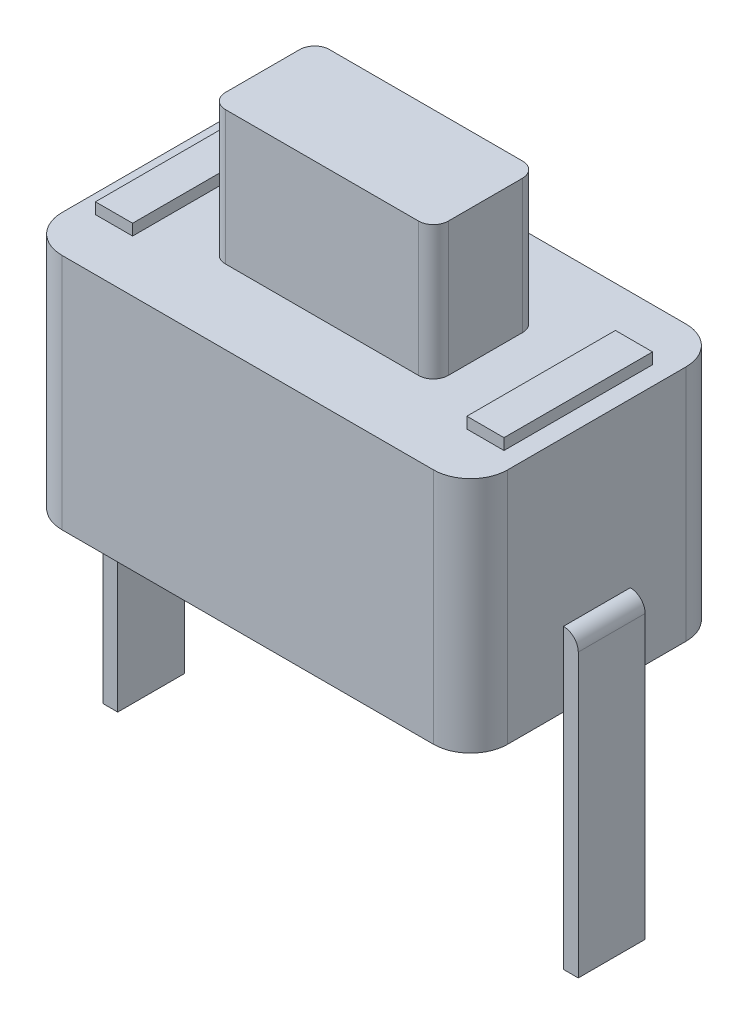
SolidWorks part; units mm, degrees
ref_plane "Front Plane" through (0, 0, 0) normal (0, 0, 1) x (1, 0, 0)
ref_plane "Top Plane" through (0, 0, 0) normal (0, 1, 0) x (1, 0, 0)
ref_plane "Right Plane" through (0, 0, 0) normal (1, 0, 0) x (0, 0, -1)
sketch "Sketch1" plane through (0, 0, 0) normal (0, 1, 0) x (1, 0, 0)
  line L1 (3, -1.7) -> (-3, -1.7)
  line L2 (3, -1.7) -> (3, 1.7)
  line L3 (3, 1.7) -> (-3, 1.7)
  line L4 (-3, -1.7) -> (-3, 1.7)
  line L5 (3, -1.7) -> (-3, 1.7) construction
  line L6 (3, 1.7) -> (-3, -1.7) construction
  point P0 (0, 0)
  dimension "D1" = 6
  dimension "D2" = 3.4
extrude "Boss-Extrude1" add sketch "Sketch1" along normal blind 3.2
sketch "Sketch2" plane through (0, 3.2, 0) normal (0, 1, 0) x (1, 0, 0)
  line L0 (-3, 1.7) -> (-3, -1.7) construction
  line L1 (1.5, -0.7) -> (-1.5, -0.7)
  line L2 (1.5, -0.7) -> (1.5, 0.7)
  line L3 (1.5, 0.7) -> (-1.5, 0.7)
  line L4 (-1.5, -0.7) -> (-1.5, 0.7)
  line L5 (1.5, -0.7) -> (-1.5, 0.7) construction
  line L6 (1.5, 0.7) -> (-1.5, -0.7) construction
  line L7 (-2.25, -1) -> (-2.75, -1)
  line L8 (-2.25, -1) -> (-2.25, 1)
  line L9 (-2.25, 1) -> (-2.75, 1)
  line L10 (-2.75, -1) -> (-2.75, 1)
  line L11 (-2.25, -1) -> (-2.75, 1) construction
  line L12 (-2.25, 1) -> (-2.75, -1) construction
  line L13 (2.75, -1) -> (2.25, -1)
  line L14 (2.75, -1) -> (2.75, 1)
  line L15 (2.75, 1) -> (2.25, 1)
  line L16 (2.25, -1) -> (2.25, 1)
  line L17 (2.75, -1) -> (2.25, 1) construction
  line L18 (2.75, 1) -> (2.25, -1) construction
  line L19 (3, -1.7) -> (3, 1.7) construction
  point P0 (0, 0)
  point P6 (-2.5, 0)
  point P11 (2.5, 0)
  point P16 (0, 0)
  point P17 (2.4808, 0)
  dimension "D1" = 3
  dimension "D2" = 1.4
  dimension "D3" = 2
  dimension "D4" = 0.5
  dimension "D5" = 0.5
  dimension "D6" = 0.5
extrude "Boss-Extrude2" add sketch "Sketch2" along normal blind 1.8 contours L4 L1 L2 L3 region at (0, 3.2, 0)
extrude "Boss-Extrude3" add sketch "Sketch2<3>" along normal blind 0.15 contours L10 L7 L8 L9 | L16 L13 L14 L15 region at (-2.5, 3.2, 0) region at (2.5, 3.2, 0)
sketch "Sketch2<3>" plane through (0, 3.2, 0) normal (0, 1, 0) x (1, 0, 0) same geometry as "Sketch2"
fillet "Fillet1" radius 0.2 4 edges at (-1.5, 4.1, -0.7) (1.5, 4.1, -0.7) (1.5, 4.1, 0.7) (-1.5, 4.1, 0.7)
sketch "Sketch3" plane through (0, 0, 0) normal (0, -1, 0) x (1, 0, 0)
  line L0 (-3, -1.7) -> (-3, 1.7) construction
  line L1 (-3, -0.45) -> (-3.2, -0.45)
  line L2 (-3, -0.45) -> (-3, 0.45)
  line L3 (-3, 0.45) -> (-3.2, 0.45)
  line L4 (-3.2, -0.45) -> (-3.2, 0.45)
  line L5 (3.2, -0.45) -> (3, -0.45)
  line L6 (3.2, -0.45) -> (3.2, 0.45)
  line L7 (3.2, 0.45) -> (3, 0.45)
  line L8 (3, -0.45) -> (3, 0.45)
  line L9 (3, 1.7) -> (3, -1.7) construction
  point P12 (-3.2, 0)
  point P14 (3.2, 0)
  dimension "D1" = 0.9
  dimension "D2" = 0.2
extrude "Boss-Extrude4" add sketch "Sketch3" along normal blind 3 and the other way blind 1
fillet "Fillet2" radius 0.2 2 edges at (3.2, 1, 0) (-3.2, 1, 0)
fillet "Fillet3" radius 0.5 4 edges at (3, 1.6, 1.7) (3, 1.6, -1.7) (-3, 1.6, -1.7) (-3, 1.6, 1.7)
equation "\"D6@Sketch2\"=\"D5@Sketch2\""
